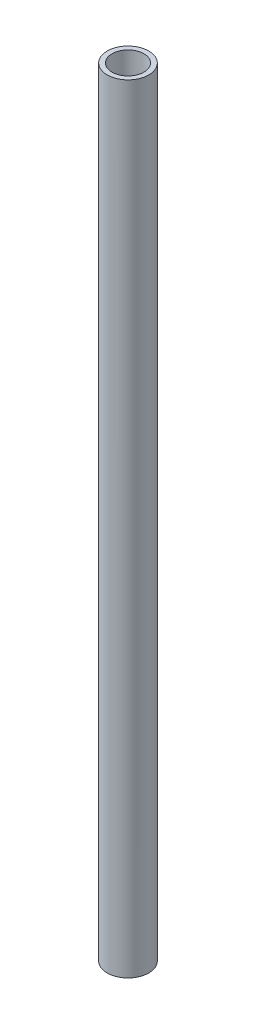
SolidWorks part; units mm, degrees
material "AISI 4130 Steel, annealed at 865C"
ref_plane "X-Y Datum" through (0, 0, 0) normal (0, 0, 1) x (1, 0, 0)
ref_plane "X-Z Datum" through (0, 0, 0) normal (0, 1, 0) x (1, 0, 0)
ref_plane "Y-Z Datum" through (0, 0, 0) normal (1, 0, 0) x (0, 0, -1)
sketch "Sketch1" plane through (0, 0, 0) normal (0, 1, 0) x (1, 0, 0)
  circle A0 centre (0, 0) radius 6.35
  circle A1 centre (0, 0) radius 4.8768
  dimension "D1" = 12.7
  dimension "D2" = 1.4732
extrude "Boss-Extrude1" add sketch "Sketch1" along normal up to surface (237.8405 mm away)
